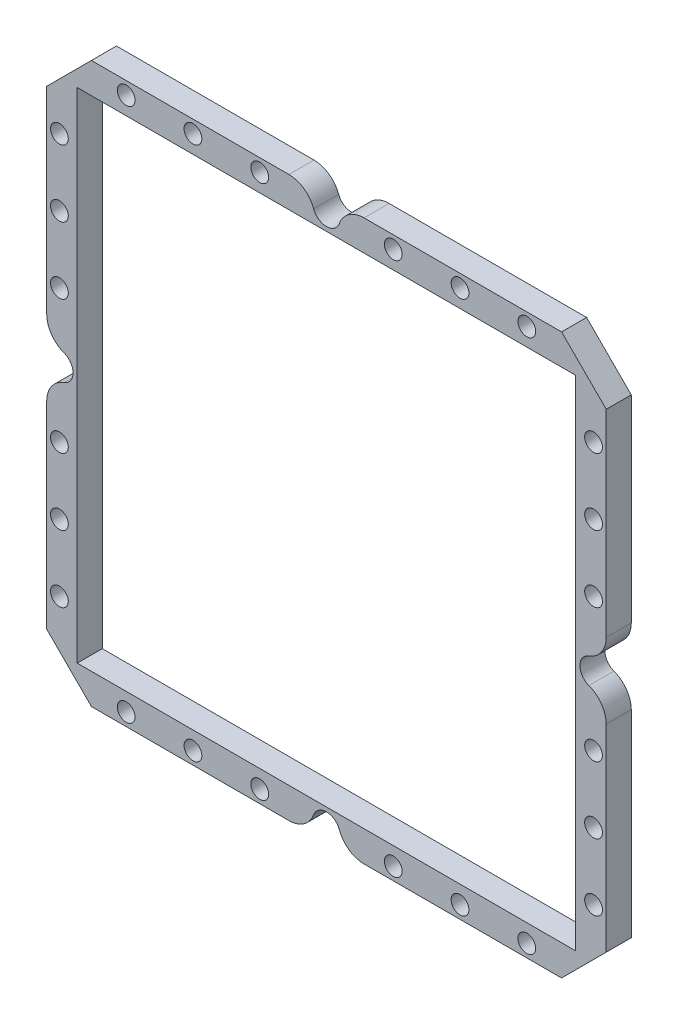
SolidWorks part; units mm, degrees
ref_plane "Front Plane" through (0, 0, 0) normal (0, 0, 1) x (1, 0, 0)
ref_plane "Top Plane" through (0, 0, 0) normal (0, 1, 0) x (1, 0, 0)
ref_plane "Right Plane" through (0, 0, 0) normal (1, 0, 0) x (0, 0, -1)
sketch "Sketch1" plane through (0, 0, 0) normal (0, 0, 1) x (1, 0, 0)
  line L0 (106.426, 0) -> (106.426, -212.852) construction
  line L1 (11.6134, -11.6134) -> (201.2386, -11.6134)
  line L2 (11.6134, -11.6134) -> (11.6134, -201.2386)
  line L3 (11.6134, -201.2386) -> (201.2386, -201.2386)
  line L4 (201.2386, -11.6134) -> (201.2386, -201.2386)
  line L5 (0, -106.426) -> (212.852, -106.426) construction
  line L6 (0, -16.9978) -> (16.9978, 0)
  line L7 (0, 0) -> (212.852, 0)
  line L8 (0, 0) -> (0, -212.852)
  line L9 (0, -212.852) -> (212.852, -212.852)
  line L10 (212.852, 0) -> (212.852, -212.852)
  line L11 (195.8542, 0) -> (212.852, -16.9978)
  line L12 (212.852, -195.8542) -> (195.8542, -212.852)
  line L13 (16.9978, -212.852) -> (0, -195.8542)
  circle A1 centre (30.226, -4.826) radius 3.38
  circle A2 centre (55.626, -4.826) radius 3.38
  circle A3 centre (81.026, -4.826) radius 3.38
  circle A5 centre (131.826, -4.826) radius 3.38
  circle A6 centre (157.226, -4.826) radius 3.38
  circle A7 centre (182.626, -4.826) radius 3.38
  circle A8 centre (208.026, -30.226) radius 3.38
  circle A9 centre (208.026, -55.626) radius 3.38
  circle A10 centre (208.026, -81.026) radius 3.38
  circle A11 centre (208.026, -106.426) radius 5.1943
  circle A12 centre (208.026, -182.626) radius 3.38
  circle A13 centre (208.026, -157.226) radius 3.38
  circle A14 centre (208.026, -131.826) radius 3.38
  circle A15 centre (182.626, -208.026) radius 3.38
  circle A16 centre (157.226, -208.026) radius 3.38
  circle A17 centre (131.826, -208.026) radius 3.38
  circle A18 centre (106.426, -208.026) radius 5.1943
  circle A19 centre (30.226, -208.026) radius 3.38
  circle A20 centre (55.626, -208.026) radius 3.38
  circle A21 centre (81.026, -208.026) radius 3.38
  circle A22 centre (4.826, -182.626) radius 3.38
  circle A23 centre (4.826, -157.226) radius 3.38
  circle A24 centre (4.826, -131.826) radius 3.38
  circle A25 centre (4.826, -106.426) radius 5.1943
  circle A26 centre (4.826, -30.226) radius 3.38
  circle A27 centre (4.826, -55.626) radius 3.38
  circle A28 centre (4.826, -81.026) radius 3.38
  circle A29 centre (106.426, -4.826) radius 3.38 [skipped]
  circle A30 centre (106.426, -4.826) radius 5.1943
  point P5 (106.426, 0)
  point P6 (106.426, -11.6134)
  point P7 (0, -106.426)
  point P12 (11.6134, -106.426)
  point P23 (0, 0)
  point P33 (106.426, -106.426)
  point P35 (106.426, -4.826)
  point P36 (106.426, -4.826)
  point P85 (106.426, -106.426)
  point P88 (0, 0)
  point P89 (0, 0)
  point P90 (0, 0)
  point P91 (208.026, -100.428)
  point P92 (0, 0)
  dimension "D4" = 6.76
  dimension "D12" = 10.3886
  dimension "D1" = 212.852
  dimension "D2" = 189.6252
  dimension "D3" = 45
  dimension "D5" = 7
  dimension "D6" = 25.4
  dimension "D7" = 12.0193
  dimension "D8" = 30.226
  dimension "D9" = 4.826
  dimension "D11" = 25.4
  dimension "D10" = 4
extrude "Boss-Extrude1" add sketch "Sketch1" along normal blind 9.525 contours L13 L9 L12 L10 L11 L7 L6 L8 A28 A27 A26 A25 A24 A23 A22 A21 A20 A19 A18 A17 A16 A15 A14 A13 A12 A11 A10 A9 A8 region at (10.6274, -10.6274, 0)
fillet "Fillet1" radius 10 8 edges at (212.852, -108.3471, 4.7625) (212.852, -104.5049, 4.7625) (104.5049, -212.852, 4.7625) (108.3471, -212.852, 4.7625) (0, -108.3471, 4.7625) (0, -104.5049, 4.7625) (108.3471, 0, 4.7625) (104.5049, 0, 4.7625)
